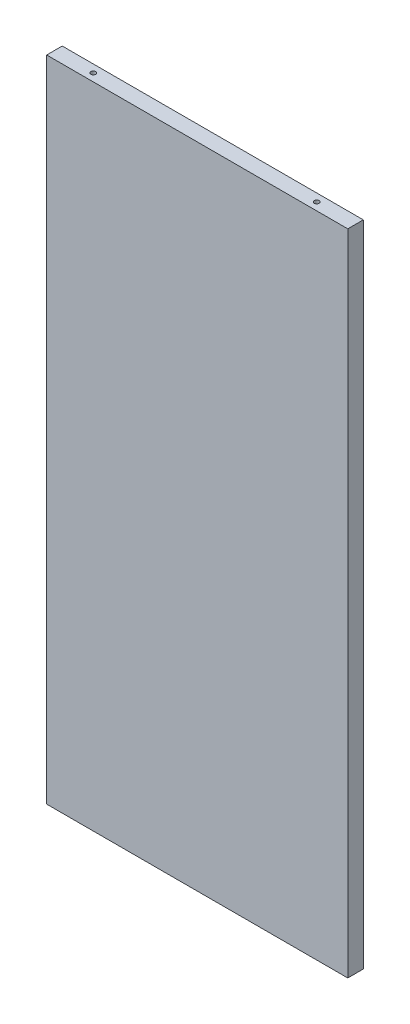
SolidWorks part; units mm, degrees
material "ДСП"
ref_plane "Спереди" through (0, 0, 0) normal (0, 0, 1) x (1, 0, 0)
ref_plane "Сверху" through (0, 0, 0) normal (0, 1, 0) x (1, 0, 0)
ref_plane "Справа" through (0, 0, 0) normal (1, 0, 0) x (0, 0, -1)
sketch "Эскиз1" plane through (0, 0, 0) normal (0, 0, 1) x (1, 0, 0)
  line L1 (0, 0) -> (310, 0)
  line L2 (0, 0) -> (0, 668)
  line L3 (0, 668) -> (310, 668)
  line L4 (310, 0) -> (310, 668)
  dimension "D1" = 668
  dimension "D2" = 310
extrude "Придание толщины" add sketch "Эскиз1" along normal blind 16
sketch "Эскиз3" plane through (0, 0, 16) normal (0, 0, 1) x (1, 0, 0)
  line L0 (0, 668) -> (0, 0) construction
  line L1 (0, 0) -> (310, 0) construction
  circle A0 centre (0, 0) radius 4
  dimension "D1" = 8
  dimension "D2" = 0
  dimension "D3" = 0
extrude "Отверстие 1" [suppressed] cut sketch "Эскиз3" against normal blind 16
sketch "Эскиз4" plane through (0, 0, 16) normal (0, 0, 1) x (1, 0, 0)
  line L0 (0, 668) -> (0, 0) construction
  line L1 (0, 0) -> (310, 0) construction
  circle A0 centre (0, 0) radius 4
  dimension "D2" = 0
  dimension "D3" = 8
extrude "Отверстие 2" [suppressed] cut sketch "Эскиз4" against normal blind 16
sketch "Эскиз5" plane through (0, 0, 16) normal (0, 0, 1) x (1, 0, 0)
  line L0 (0, 668) -> (0, 0) construction
  line L1 (0, 0) -> (310, 0) construction
  circle A0 centre (0, 0) radius 4
  dimension "D1" = 8
extrude "Отверстие 3" [suppressed] cut sketch "Эскиз5" against normal blind 16
sketch "Эскиз6" plane through (0, 0, 16) normal (0, 0, 1) x (1, 0, 0)
  line L0 (0, 668) -> (0, 0) construction
  line L1 (0, 0) -> (310, 0) construction
  circle A0 centre (0, 0) radius 4
  dimension "D1" = 8
extrude "Отверстие 4" [suppressed] cut sketch "Эскиз6" against normal blind 16
sketch "Эскиз7" plane through (0, 0, 16) normal (0, 0, 1) x (1, 0, 0)
  line L0 (0, 668) -> (0, 0) construction
  line L1 (0, 0) -> (310, 0) construction
  circle A0 centre (0, 0) radius 4
  dimension "D1" = 8
extrude "Отверстие 5" [suppressed] cut sketch "Эскиз7" against normal blind 16
sketch "Эскиз8" plane through (0, 0, 16) normal (0, 0, 1) x (1, 0, 0)
  line L0 (0, 668) -> (0, 0) construction
  line L1 (0, 0) -> (310, 0) construction
  circle A0 centre (0, 0) radius 4
  dimension "D1" = 8
extrude "Отверстие 6" [suppressed] cut sketch "Эскиз8" against normal blind 16
sketch "Эскиз9" plane through (0, 0, 16) normal (0, 0, 1) x (1, 0, 0)
  line L0 (0, 668) -> (0, 0) construction
  line L1 (0, 0) -> (310, 0) construction
  circle A0 centre (0, 0) radius 4
  dimension "D1" = 8
extrude "Отверстие 7" [suppressed] cut sketch "Эскиз9" against normal blind 16
sketch "Эскиз10" plane through (0, 0, 16) normal (0, 0, 1) x (1, 0, 0)
  line L0 (0, 668) -> (0, 0) construction
  line L1 (0, 0) -> (310, 0) construction
  circle A0 centre (0, 0) radius 4
  dimension "D1" = 8
extrude "Отверстие 8" [suppressed] cut sketch "Эскиз10" against normal blind 16
sketch "Эскиз27" plane through (0, 0, 16) normal (0, 0, 1) x (1, 0, 0)
  line L2 (0, 668) -> (0, 0) construction
  line L3 (0, 0) -> (310, 0) construction
  circle A0 centre (0, 0) radius 4
  dimension "D1" = 8
  dimension "D3" = 0
extrude "Отверстие 9" [suppressed] cut sketch "Эскиз27" against normal blind 10
sketch "Эскиз29" plane through (0, 0, 16) normal (0, 0, 1) x (1, 0, 0)
  line L2 (0, 668) -> (0, 0) construction
  line L3 (0, 0) -> (310, 0) construction
  circle A0 centre (0, 0) radius 4
  dimension "D1" = 8
extrude "Отверстие 10" [suppressed] cut sketch "Эскиз29" against normal blind 10
sketch "Эскиз30" plane through (0, 0, 16) normal (0, 0, 1) x (1, 0, 0)
  line L1 (0, 0) -> (310, 0) construction
  line L3 (0, 668) -> (0, 0) construction
  circle A0 centre (0, 0) radius 4
  dimension "D1" = 8
extrude "Отверстие 11" [suppressed] cut sketch "Эскиз30" against normal blind 10
sketch "Эскиз31" plane through (0, 0, 16) normal (0, 0, 1) x (1, 0, 0)
  line L2 (0, 0) -> (310, 0) construction
  line L3 (0, 668) -> (0, 0) construction
  circle A0 centre (0, 0) radius 4
  dimension "D1" = 8
extrude "Отверстие 12" [suppressed] cut sketch "Эскиз31" against normal blind 10
sketch "Эскиз11" plane through (0, 668, 0) normal (0, 1, 0) x (1, 0, 0)
  line L0 (0, -16) -> (0, 0) construction
  line L1 (310, -16) -> (0, -16) construction
  circle A0 centre (40, -8) radius 2.5
  dimension "D3" = 8
  dimension "D1" = 5
  dimension "D2" = 40
extrude "Отверстие А1" cut sketch "Эскиз11" against normal blind 37
sketch "Эскиз12" plane through (0, 668, 0) normal (0, 1, 0) x (1, 0, 0)
  line L1 (0, -16) -> (0, 0) construction
  line L2 (310, -16) -> (0, -16) construction
  circle A0 centre (270, -8) radius 2.5
  dimension "D3" = 8
  dimension "D1" = 5
  dimension "D2" = 270
extrude "Отверстие А2" cut sketch "Эскиз12" against normal blind 37
sketch "Эскиз13" plane through (0, 668, 0) normal (0, 1, 0) x (1, 0, 0)
  line L1 (0, -16) -> (0, 0) construction
  line L2 (310, -16) -> (0, -16) construction
  circle A0 centre (0, -16) radius 4
  dimension "D1" = 8
  dimension "D3" = 0
extrude "Отверстие А3" [suppressed] cut sketch "Эскиз13" against normal blind 20
sketch "Эскиз14" plane through (0, 668, 0) normal (0, 1, 0) x (1, 0, 0)
  line L0 (0, -16) -> (0, 0) construction
  line L1 (310, -16) -> (0, -16) construction
  circle A0 centre (0, -8) radius 4
  dimension "D1" = 8
  dimension "D3" = 8
extrude "Отверстие А4" [suppressed] cut sketch "Эскиз14" against normal blind 20
sketch "Эскиз15" plane through (310, 0, 0) normal (1, 0, 0) x (0, 0, -1)
  line L0 (-16, 668) -> (0, 668) construction
  line L1 (-16, 0) -> (-16, 668) construction
  circle A0 centre (-16, 668) radius 2.5
  dimension "D2" = 0
  dimension "D3" = 0
  dimension "D1" = 5
extrude "Отверстие В1" [suppressed] cut sketch "Эскиз15" against normal blind 37
sketch "Эскиз16" plane through (310, 0, 0) normal (1, 0, 0) x (0, 0, -1)
  line L0 (-16, 668) -> (0, 668) construction
  line L1 (-16, 0) -> (-16, 668) construction
  circle A0 centre (-16, 668) radius 2.5
  dimension "D1" = 5
extrude "Отверстие В2" [suppressed] cut sketch "Эскиз16" against normal blind 37
sketch "Эскиз17" plane through (310, 0, 0) normal (1, 0, 0) x (0, 0, -1)
  line L1 (-16, 668) -> (0, 668) construction
  line L2 (-16, 0) -> (-16, 668) construction
  circle A0 centre (-16, 668) radius 4
  dimension "D1" = 8
  dimension "D2" = 0
  dimension "D3" = 0
extrude "Отверстие В3" [suppressed] cut sketch "Эскиз17" against normal blind 20
sketch "Эскиз18" plane through (310, 0, 0) normal (1, 0, 0) x (0, 0, -1)
  line L0 (-16, 668) -> (0, 668) construction
  line L1 (-16, 0) -> (-16, 668) construction
  circle A0 centre (-16, 668) radius 4
  dimension "D3" = 0
  dimension "D1" = 0
  dimension "D2" = 8
extrude "Отверстие В4" [suppressed] cut sketch "Эскиз18" against normal blind 20
sketch "Эскиз19" plane through (0, 0, 0) normal (0, -1, 0) x (1, 0, 0)
  line L0 (310, 16) -> (310, 0) construction
  line L1 (0, 16) -> (310, 16) construction
  circle A0 centre (270, 8) radius 2.5
  dimension "D3" = 8
  dimension "D1" = 5
  dimension "D2" = 40
extrude "Отверстие С1" cut sketch "Эскиз19" against normal blind 37
sketch "Эскиз20" plane through (0, 0, 0) normal (0, -1, 0) x (1, 0, 0)
  line L0 (310, 16) -> (310, 0) construction
  line L1 (0, 16) -> (310, 16) construction
  circle A0 centre (40, 8) radius 2.5
  dimension "D3" = 8
  dimension "D2" = 5
  dimension "D1" = 270
extrude "Отверстие С2" cut sketch "Эскиз20" against normal blind 37
sketch "Эскиз21" plane through (0, 0, 0) normal (0, -1, 0) x (1, 0, 0)
  line L0 (310, 16) -> (310, 0) construction
  line L1 (0, 16) -> (310, 16) construction
  circle A0 centre (310, 16) radius 4
  dimension "D1" = 8
  dimension "D2" = 0
  dimension "D3" = 0
extrude "Отверстие С3" [suppressed] cut sketch "Эскиз21" against normal blind 20
sketch "Эскиз22" plane through (0, 0, 0) normal (0, -1, 0) x (1, 0, 0)
  line L0 (310, 16) -> (310, 0) construction
  line L1 (0, 16) -> (310, 16) construction
  circle A0 centre (310, 16) radius 4
  dimension "D1" = 8
  dimension "D2" = 0
  dimension "D3" = 0
extrude "Отверстие С4" [suppressed] cut sketch "Эскиз22" against normal blind 20
sketch "Эскиз23" plane through (0, 0, 0) normal (-1, 0, 0) x (0, 0, 1)
  line L0 (16, 0) -> (0, 0) construction
  line L1 (16, 668) -> (16, 0) construction
  circle A0 centre (16, 0) radius 2.5
  dimension "D2" = 0
  dimension "D3" = 0
  dimension "D1" = 5
extrude "Отверстие Д1" [suppressed] cut sketch "Эскиз23" against normal blind 37
sketch "Эскиз24" plane through (0, 0, 0) normal (-1, 0, 0) x (0, 0, 1)
  line L0 (16, 0) -> (0, 0) construction
  line L1 (16, 668) -> (16, 0) construction
  circle A0 centre (16, 0) radius 2.5
  dimension "D2" = 0
  dimension "D3" = 0
  dimension "D1" = 5
extrude "Отверстие Д2" [suppressed] cut sketch "Эскиз24" against normal blind 37
sketch "Эскиз25" plane through (0, 0, 0) normal (-1, 0, 0) x (0, 0, 1)
  line L0 (16, 0) -> (0, 0) construction
  line L1 (16, 668) -> (16, 0) construction
  circle A0 centre (16, 0) radius 4
  dimension "D1" = 8
  dimension "D2" = 0
  dimension "D3" = 0
extrude "Отверстие Д3" [suppressed] cut sketch "Эскиз25" against normal blind 20
sketch "Эскиз26" plane through (0, 0, 0) normal (-1, 0, 0) x (0, 0, 1)
  line L0 (16, 0) -> (0, 0) construction
  line L1 (16, 668) -> (16, 0) construction
  circle A0 centre (16, 0) radius 4
  dimension "D1" = 8
  dimension "D2" = 0
  dimension "D3" = 0
extrude "Отверстие Д4" [suppressed] cut sketch "Эскиз26" against normal blind 20
equation "\"D1@Придание толщины\" = \"Thick\""
equation "\"D2@Эскиз1\"=\"Width\""
equation "\"D1@Эскиз1\"=\"Height\""
equation "\"D1\" = 0"
equation "\"X1\" = 0"
equation "\"Y1\" = 0"
equation "\"H1\" = 0"
equation "\"D1@Эскиз3\"=\"D1\""
equation "\"D2@Эскиз3\"=\"X1\""
equation "\"D3@Эскиз3\"=\"Y1\""
equation "\"D1@Отверстие 1\"=\"H1\""
equation "\"D2\" = 0"
equation "\"X2\" = 0"
equation "\"Y2\" = 0"
equation "\"H2\" = 0"
equation "\"D3\" = 0"
equation "\"X3\" = 0"
equation "\"Y3\" = 0"
equation "\"H3\" = 0"
equation "\"D4\" = 0"
equation "\"X4\" = 0"
equation "\"Y4\" = 0"
equation "\"H4\" = 0"
equation "\"D5\" = 0"
equation "\"X5\" = 0"
equation "\"Y5\" = 0"
equation "\"H5\" = 0"
equation "\"D6\" = 0"
equation "\"X6\" = 0"
equation "\"Y6\" = 0"
equation "\"H6\" = 0"
equation "\"D7\" = 0"
equation "\"X7\" = 0"
equation "\"Y7\" = 0"
equation "\"H7\" = 0"
equation "\"D8\" = 0"
equation "\"X8\" = 0"
equation "\"Y8\" = 0"
equation "\"H8\" = 0"
equation "\"D3@Эскиз4\"=\"D2\""
equation "\"D1@Эскиз4\"=\"X2\""
equation "\"D2@Эскиз4\"=\"Y2\""
equation "\"D1@Отверстие 2\"=\"H2\""
equation "\"D2@Эскиз5\"=\"X3\""
equation "\"D1@Эскиз5\"=\"D3\""
equation "\"D3@Эскиз5\"=\"Y3\""
equation "\"D1@Отверстие 3\" = \"H3\""
equation "\"D1@Эскиз6\"=\"D4\""
equation "\"D2@Эскиз6\"=\"X4\""
equation "\"D3@Эскиз6\"=\"Y4\""
equation "\"D1@Отверстие 4\" = \"H4\""
equation "\"D1@Эскиз7\"=\"D5\""
equation "\"D2@Эскиз7\"=\"X5\""
equation "\"D3@Эскиз7\"=\"Y5\""
equation "\"D1@Отверстие 5\" = \"H5\""
equation "\"D1@Эскиз8\"=\"D6\""
equation "\"D2@Эскиз8\"=\"X6\""
equation "\"D3@Эскиз8\"=\"Y6\""
equation "\"D1@Отверстие 6\" = \"H6\""
equation "\"D1@Эскиз9\"=\"D7\""
equation "\"D2@Эскиз9\"=\"X7\""
equation "\"D3@Эскиз9\"=\"Y7\""
equation "\"D1@Отверстие 7\" = \"H7\""
equation "\"D1@Эскиз10\"=\"D8\""
equation "\"D2@Эскиз10\"=\"X8\""
equation "\"D3@Эскиз10\"=\"Y8\""
equation "\"D1@Отверстие 8\" = \"H8\""
equation "\"Отверстие 1\"= IIF ( \"D1\" = 0 , \"suppressed\" , \"unsuppressed\" )"
equation "\"Отверстие 2\"= IIF ( \"D2\" = 0 , \"suppressed\" , \"unsuppressed\" )"
equation "\"Отверстие 3\"= IIF ( \"D3\" = 0 , \"suppressed\" , \"unsuppressed\" )"
equation "\"Отверстие 4\"= IIF ( \"D4\" = 0 , \"suppressed\" , \"unsuppressed\" )"
equation "\"Отверстие 5\"= IIF ( \"D5\" = 0 , \"suppressed\" , \"unsuppressed\" )"
equation "\"Отверстие 6\" = IIF ( \"D6\" = 0 , \"suppressed\" , \"unsuppressed\" )"
equation "\"Отверстие 7\"= IIF ( \"D7\" = 0 , \"suppressed\" , \"unsuppressed\" )"
equation "\"Отверстие 8\"= IIF ( \"D8\" = 0 , \"suppressed\" , \"unsuppressed\" )"
equation "\"DA1\" = 5"
equation "\"XA1\" = 40"
equation "\"YA1\" = 8"
equation "\"HA1\" = 37"
equation "\"DA2\" = 5"
equation "\"XA2\" = 270"
equation "\"YA2\" = 8"
equation "\"HA2\" = 37"
equation "\"DA3\" = 0"
equation "\"XA3\" = 0"
equation "\"YA3\" = 0"
equation "\"DA4\" = 0"
equation "\"XA4\" = 0"
equation "\"YA4\" = 0"
equation "\"HA4\" = 0"
equation "\"D1@Эскиз11\"=\"DA1\""
equation "\"D2@Эскиз11\"=\"XA1\""
equation "\"D3@Эскиз11\"=\"YA1\""
equation "\"D1@Отверстие А1\" = \"HA1\""
equation "\"D1@Эскиз12\"=\"DA2\""
equation "\"D2@Эскиз12\"=\"XA2\""
equation "\"HA3\" = 0"
equation "\"D1@Эскиз13\"=\"DA3\""
equation "\"D2@Эскиз13\"=\"XA3\""
equation "\"D3@Эскиз13\"=\"YA3\""
equation "\"D1@Отверстие А3\" = \"HA3\""
equation "\"D1@Отверстие А2\" = \"HA2\""
equation "\"D1@Эскиз14\"=\"DA4\""
equation "\"D2@Эскиз14\"=\"XA4\""
equation "\"Отверстие А1\"= IIF ( \"DA1\" = 0 , \"suppressed\" , \"unsuppressed\" )"
equation "\"Отверстие А2\"= IIF ( \"DA2\" = 0 , \"suppressed\" , \"unsuppressed\" )"
equation "\"Отверстие А3\"= IIF ( \"DA3\" = 0 , \"suppressed\" , \"unsuppressed\" )"
equation "\"Отверстие А4\"= IIF ( \"DA4\" = 0 , \"suppressed\" , \"unsuppressed\" )"
equation "\"DB1\" = 0"
equation "\"XB1\" = 0"
equation "\"YB1\" = 0"
equation "\"HB1\" = 0"
equation "\"DB2\" = 0"
equation "\"XB2\" = 0"
equation "\"YB2\" = 0"
equation "\"HB2\" = 0"
equation "\"DB3\" = 0"
equation "\"XB3\" = 0"
equation "\"YB3\" = 0"
equation "\"HB3\" = 0"
equation "\"DB4\" = 0"
equation "\"XB4\" = 0"
equation "\"YB4\" = 0"
equation "\"HB4\" = 0"
equation "\"DC1\" = 5"
equation "\"XC1\" = 40"
equation "\"YC1\" = 8"
equation "\"HC1\" = 37"
equation "\"DC2\" = 5"
equation "\"XC2\" = 270"
equation "\"YC2\" = 8"
equation "\"HC2\" = 37"
equation "\"DC3\" = 0"
equation "\"XC3\" = 0"
equation "\"YC3\" = 0"
equation "\"HC3\" = 0"
equation "\"DC4\" = 0"
equation "\"XC4\" = 0"
equation "\"YC4\" = 0"
equation "\"HC4\" = 0"
equation "\"DD1\" = 0"
equation "\"XD1\" = 0"
equation "\"YD1\" = 0"
equation "\"HD1\" = 0"
equation "\"DD2\" = 0"
equation "\"XD2\" = 0"
equation "\"YD2\" = 0"
equation "\"HD2\" = 0"
equation "\"DD3\" = 0"
equation "\"XD3\" = 0"
equation "\"YD3\" = 0"
equation "\"HD3\" = 0"
equation "\"DD4\" = 0"
equation "\"XD4\" = 0"
equation "\"YD4\" = 0"
equation "\"HD4\" = 0"
equation "\"D1@Эскиз15\"=\"DB1\""
equation "\"D2@Эскиз15\"=\"XB1\""
equation "\"D3@Эскиз15\"=\"YB1\""
equation "\"D1@Отверстие В1\" = \"HB1\""
equation "\"D1@Эскиз16\"=\"DB2\""
equation "\"D2@Эскиз16\"=\"XB2\""
equation "\"D3@Эскиз16\"=\"YB2\""
equation "\"D1@Отверстие В2\" = \"HB2\""
equation "\"D1@Эскиз17\"=\"DB3\""
equation "\"D2@Эскиз17\"=\"XB3\""
equation "\"D3@Эскиз17\"=\"YB3\""
equation "\"D1@Отверстие В3\" = \"HB3\""
equation "\"D1@Эскиз18\"=\"XB4\""
equation "\"D2@Эскиз18\"=\"DB4\""
equation "\"D3@Эскиз18\"=\"YB4\""
equation "\"D1@Отверстие В4\" = \"HB4\""
equation "\"D1@Эскиз19\"=\"DC1\""
equation "\"D2@Эскиз19\"=\"XC1\""
equation "\"D3@Эскиз19\"=\"YC1\""
equation "\"D1@Отверстие С1\" = \"HC1\""
equation "\"D1@Эскиз20\"=\"XC2\""
equation "\"D2@Эскиз20\"=\"DC2\""
equation "\"D3@Эскиз20\"=\"YC2\""
equation "\"D1@Отверстие С2\" = \"HC2\""
equation "\"D1@Эскиз21\"=\"DC3\""
equation "\"D2@Эскиз21\"=\"XC3\""
equation "\"D3@Эскиз21\"=\"YC3\""
equation "\"D1@Отверстие С3\" = \"HC3\""
equation "\"D1@Эскиз22\"=\"DC4\""
equation "\"D2@Эскиз22\"=\"XC4\""
equation "\"D3@Эскиз22\"=\"YC4\""
equation "\"D1@Отверстие С4\" = \"HC4\""
equation "\"D1@Эскиз23\"=\"DD1\""
equation "\"D2@Эскиз23\"=\"XD1\""
equation "\"D3@Эскиз23\"=\"YD1\""
equation "\"D1@Отверстие Д1\" = \"HD1\""
equation "\"D1@Эскиз24\"=\"DD2\""
equation "\"D2@Эскиз24\"=\"XD2\""
equation "\"D3@Эскиз24\"=\"YD2\""
equation "\"D1@Отверстие Д2\" = \"HD2\""
equation "\"D1@Эскиз25\"=\"DD3\""
equation "\"D2@Эскиз25\"=\"XD3\""
equation "\"D3@Эскиз25\"=\"YD3\""
equation "\"D1@Отверстие Д3\" = \"HD3\""
equation "\"D1@Эскиз26\"=\"DD4\""
equation "\"D2@Эскиз26\"=\"XD4\""
equation "\"D3@Эскиз26\"=\"YD4\""
equation "\"D1@Отверстие Д4\" = \"HD4\""
equation "\"Отверстие В1\"= IIF ( \"DB1\" = 0 , \"suppressed\" , \"unsuppressed\" )"
equation "\"Отверстие В2\"= IIF ( \"DB2\" = 0 , \"suppressed\" , \"unsuppressed\" )"
equation "\"Отверстие В3\"= IIF ( \"DB3\" = 0 , \"suppressed\" , \"unsuppressed\" )"
equation "\"Отверстие В4\"= IIF ( \"DB4\" = 0 , \"suppressed\" , \"unsuppressed\" )"
equation "\"Отверстие С1\"= IIF ( \"DC1\" = 0 , \"suppressed\" , \"unsuppressed\" )"
equation "\"Отверстие С2\"= IIF ( \"DC2\" = 0 , \"suppressed\" , \"unsuppressed\" )"
equation "\"Отверстие С3\"= IIF ( \"DC3\" = 0 , \"suppressed\" , \"unsuppressed\" )"
equation "\"Отверстие С4\"= IIF ( \"DC4\" = 0 , \"suppressed\" , \"unsuppressed\" )"
equation "\"Отверстие Д1\"= IIF ( \"DD1\" = 0 , \"suppressed\" , \"unsuppressed\" )"
equation "\"Отверстие Д2\"= IIF ( \"DD2\" = 0 , \"suppressed\" , \"unsuppressed\" )"
equation "\"Отверстие Д3\"= IIF ( \"DD3\" = 0 , \"suppressed\" , \"unsuppressed\" )"
equation "\"Отверстие Д4\"= IIF ( \"DD4\" = 0 , \"suppressed\" , \"unsuppressed\" )"
equation "\"D9\" = 0"
equation "\"X9\" = 0"
equation "\"Y9\" = 0"
equation "\"H9\" = 0"
equation "\"D10\" = 0"
equation "\"X10\" = 0"
equation "\"Y10\" = 0"
equation "\"H10\" = 0"
equation "\"D11\" = 0"
equation "\"X11\" = 0"
equation "\"Y11\" = 0"
equation "\"H11\" = 0"
equation "\"D12\" = 0"
equation "\"X12\" = 0"
equation "\"Y12\" = 0"
equation "\"H12\" = 0"
equation "\"D1@Эскиз27\"=\"D9\""
equation "\"D2@Эскиз27\"=\"X9\""
equation "\"D3@Эскиз27\"=\"Y9\""
equation "\"D1@Отверстие 9\" = \"H9\""
equation "\"D1@Эскиз29\"=\"D10\""
equation "\"D2@Эскиз29\"=\"X10\""
equation "\"D3@Эскиз29\"=\"Y10\""
equation "\"D1@Отверстие 10\" = \"H10\""
equation "\"D1@Эскиз30\"=\"D11\""
equation "\"D2@Эскиз30\"=\"X11\""
equation "\"D3@Эскиз30\"=\"Y11\""
equation "\"D1@Отверстие 11\" = \"H11\""
equation "\"D1@Эскиз31\"=\"D12\""
equation "\"D2@Эскиз31\"=\"X12\""
equation "\"D3@Эскиз31\"=\"Y12\""
equation "\"D1@Отверстие 12\" = \"H12\""
equation "\"Отверстие 9\"= IIF ( \"D9\" = 0 , \"suppressed\" , \"unsuppressed\" )"
equation "\"Отверстие 10\"= IIF ( \"D10\" = 0 , \"suppressed\" , \"unsuppressed\" )"
equation "\"Отверстие 11\"= IIF ( \"D11\" = 0 , \"suppressed\" , \"unsuppressed\" )"
equation "\"Отверстие 12\"= IIF ( \"D12\" = 0 , \"suppressed\" , \"unsuppressed\" )"
equation "\"Height\" = 668"
equation "\"Width\" = 310"
equation "\"Thick\" = 16"
equation "\"D3@Эскиз12\"=\"YA2\""
